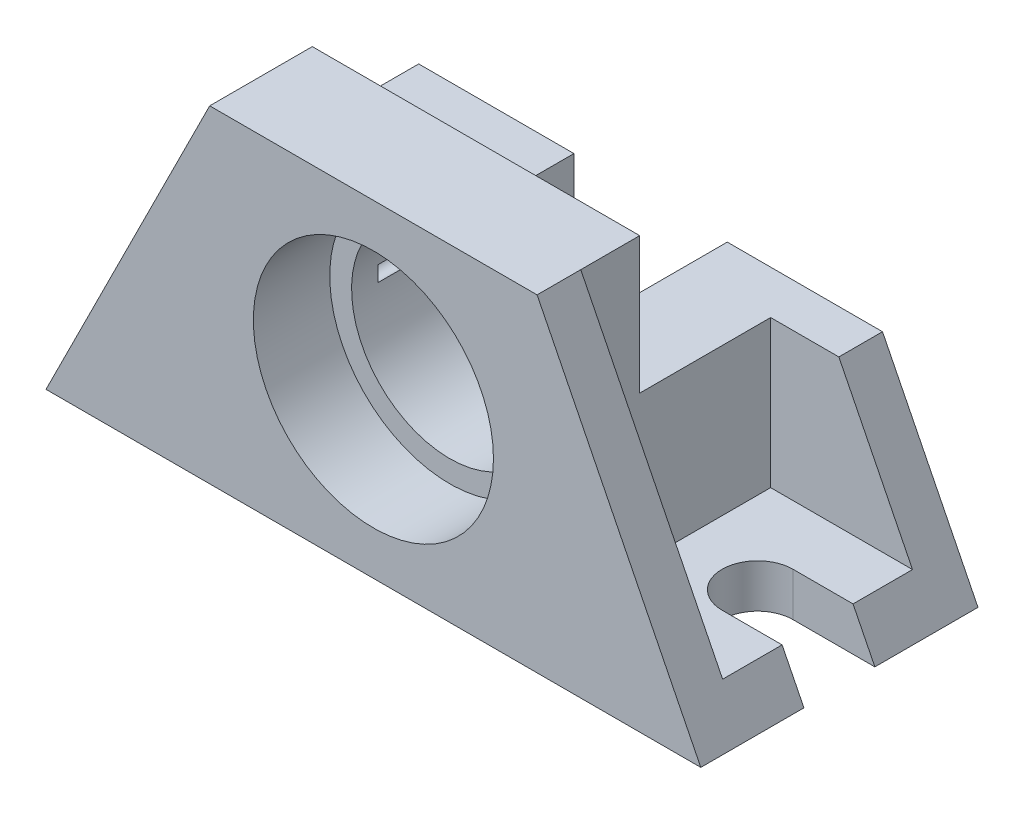
SolidWorks part; units mm, degrees
ref_plane "Front Plane" through (0, 0, 0) normal (0, 0, 1) x (1, 0, 0)
ref_plane "Top Plane" through (0, 0, 0) normal (0, 1, 0) x (1, 0, 0)
ref_plane "Right Plane" through (0, 0, 0) normal (1, 0, 0) x (0, 0, -1)
sketch "Sketch3" plane through (0, 0, 0) normal (0, 0, 1) x (1, 0, 0)
  line L0 (-30, -15) -> (30, -15)
  line L1 (30, -15) -> (15, 15)
  line L2 (15, 15) -> (-15, 15)
  line L3 (-15, 15) -> (-30, -15)
  line L4 (0, 15) -> (0, -15) construction
  circle A0 centre (0, 0) radius 9
  dimension "D4" = 18
  dimension "D1" = 30
  dimension "D2" = 30
  dimension "D3" = 60
extrude "Boss-Extrude3" add sketch "Sketch3" along normal blind 25.4
sketch "Sketch4" plane through (0, 15, 0) normal (0, 1, 0) x (1, 0, 0)
  line L0 (0, -25.4) -> (0, 0) construction
  line L1 (15, -25.4) -> (-15, -25.4) construction
  line L3 (30, -21.4) -> (12, -21.4)
  line L4 (-30, -21.4) -> (30, -21.4) construction
  line L5 (-30, -21.4) -> (-30, -4) construction
  line L6 (-30, -4) -> (30, -4) construction
  line L7 (30, -21.4) -> (30, -4) construction
  line L8 (-30, -21.4) -> (30, -4) construction
  line L9 (-30, -4) -> (30, -21.4) construction
  line L14 (30, -21.4) -> (30, -4)
  line L19 (15, 0) -> (-15, 0) construction
  line L20 (30, -25.4) -> (30, 0) construction
  line L21 (30, -4) -> (12, -4)
  line L22 (12, -21.4) -> (12, -4)
  line L23 (-30, -21.4) -> (-12, -21.4)
  line L24 (-30, -21.4) -> (-30, -4)
  line L25 (-30, -4) -> (-12, -4)
  line L26 (-12, -21.4) -> (-12, -4)
  point P6 (0, -12.7)
  line M4 (-15, 0) -> (-15, -25.4)
  line M6 (15, -25.4) -> (15, 0)
  dimension "D1" = 4
  dimension "D2" = 18
  dimension "D3" = 4
  dimension "D4" = 18
extrude "Cut-Extrude2" cut sketch "Sketch4" against normal blind 26 contours L4 M4 | L14 L21 L3 M6 | L4 L7 L6 L5 region at (22.5, 15, 12.7) region at (-22.5, 15, 12.7)
sketch "Sketch5" plane through (0, 0, 0) normal (0, 0, -1) x (-1, 0, 0)
  line L0 (-9.525, 0) -> (9.525, 0) construction
  line L1 (-9.525, 8.7666) -> (-9.525, -11) construction
  line L3 (9.525, 8.4673) -> (9.525, -11) construction
  line L4 (-12.025, 2.5) -> (-12.025, -15)
  line L5 (-12.025, 2.5) -> (-7.025, 2.5)
  line L6 (-12.025, -15) -> (-7.025, -15)
  line L7 (-7.025, 2.5) -> (-7.025, -15)
  line L8 (-12.025, 2.5) -> (-7.025, -15) construction
  line L9 (-12.025, -15) -> (-7.025, 2.5) construction
  line L10 (7.025, 2.5) -> (7.025, -15)
  line L11 (7.025, 2.5) -> (12.025, 2.5)
  line L12 (7.025, -15) -> (12.025, -15)
  line L13 (12.025, 2.5) -> (12.025, -15)
  line L14 (7.025, 2.5) -> (12.025, -15) construction
  line L15 (7.025, -15) -> (12.025, 2.5) construction
  line L18 (30, -15) -> (-30, -15) construction
  circle A0 centre (9.525, 0) radius 0.9
  circle A1 centre (-9.525, 0) radius 0.9
  point P3 (0, 0)
  point P14 (-9.525, -6.25)
  point P15 (9.525, -6.25)
  dimension "D2" = 1.8
  dimension "D3" = 1.8
  dimension "D1" = 19.05
  dimension "D4" = 5
  dimension "D5" = 5
  dimension "D6" = 2.5
extrude "Boss-Extrude4" add sketch "Sketch5" against normal blind 10 contours L10 L12 L13 L11 | L7 L6 L4 L5
sketch "Sketch6" plane through (0, 0, 0) normal (0, 0, -1) x (-1, 0, 0)
  line L0 (7.025, 2.5) -> (8.6458, 2.5) construction
  line L1 (-30, 2.5) -> (30, 2.5)
  line L2 (-30, 2.5) -> (-30, 15)
  line L3 (-30, 15) -> (30, 15)
  line L4 (30, 2.5) -> (30, 15)
  line L6 (-15, 15) -> (15, 15) construction
extrude "Cut-Extrude3" cut sketch "Sketch6" against normal blind 16
sketch "Sketch7" plane through (0, -15, 0) normal (0, -1, 0) x (1, 0, 0)
  line L0 (0, 0) -> (0, 25.4) construction
  line L5 (12.5, 9.45) -> (-12.5, 9.45)
  line L6 (12.5, 9.45) -> (12.5, 15.95)
  line L7 (12.5, 15.95) -> (-12.5, 15.95)
  line L8 (-12.5, 9.45) -> (-12.5, 15.95)
  line L9 (-30, 25.4) -> (30, 25.4) construction
  line L10 (30, 12.7) -> (-30, 12.7) construction
  line L11 (30, 25.4) -> (30, 0) construction
  line L12 (-30, 25.4) -> (-30, 0) construction
  point P9 (0, 9.45)
  point P16 (-12.5, 12.7)
  dimension "D1" = 6.5
  dimension "D2" = 25
extrude "Boss-Extrude5" add sketch "Sketch7" along normal blind 4
sketch "Sketch8" plane through (0, -15, 0) normal (0, -1, 0) x (1, 0, 0)
  line L0 (30, 12.7) -> (-30, 12.7) construction
  line L1 (30, 25.4) -> (30, 0) construction
  line L2 (-30, 25.4) -> (-30, 0) construction
  line L3 (-37.5, 12.7) -> (-22.5, 12.7) construction
  line L4 (37.5, 12.7) -> (22.5, 12.7) construction
  line L5 (37.5, 9.45) -> (22.5, 9.45)
  line L6 (37.5, 15.95) -> (22.5, 15.95)
  line L7 (-37.5, 15.95) -> (-22.5, 15.95)
  line L8 (-37.5, 9.45) -> (-22.5, 9.45)
  arc A0 (37.5, 9.45) -> (37.5, 15.95) centre (37.5, 12.7) ccw
  arc A1 (22.5, 15.95) -> (22.5, 9.45) centre (22.5, 12.7) ccw
  arc A2 (-37.5, 15.95) -> (-37.5, 9.45) centre (-37.5, 12.7) ccw
  arc A3 (-22.5, 9.45) -> (-22.5, 15.95) centre (-22.5, 12.7) ccw
  point P10 (30, 12.7)
  point P16 (-30, 12.7)
  dimension "D1" = 6.5
  dimension "D2" = 7.5
  dimension "D3" = 6.5
  dimension "D4" = 7.5
extrude "Cut-Extrude4" cut sketch "Sketch8" against normal through all
sketch "Sketch9" plane through (0, 0, 25.4) normal (0, 0, 1) x (1, 0, 0)
  circle A0 centre (0, 0) radius 11
  dimension "D1" = 22
extrude "Cut-Extrude5" cut sketch "Sketch9" against normal blind 7
extrude "Cut-Extrude6" cut sketch "Sketch5<3>" against normal up to surface (16 mm away) contours A0 | A1 up to face at (0, 7.75, 16)
sketch "Sketch5<3>" plane through (0, 0, 0) normal (0, 0, -1) x (-1, 0, 0) same geometry as "Sketch5"
